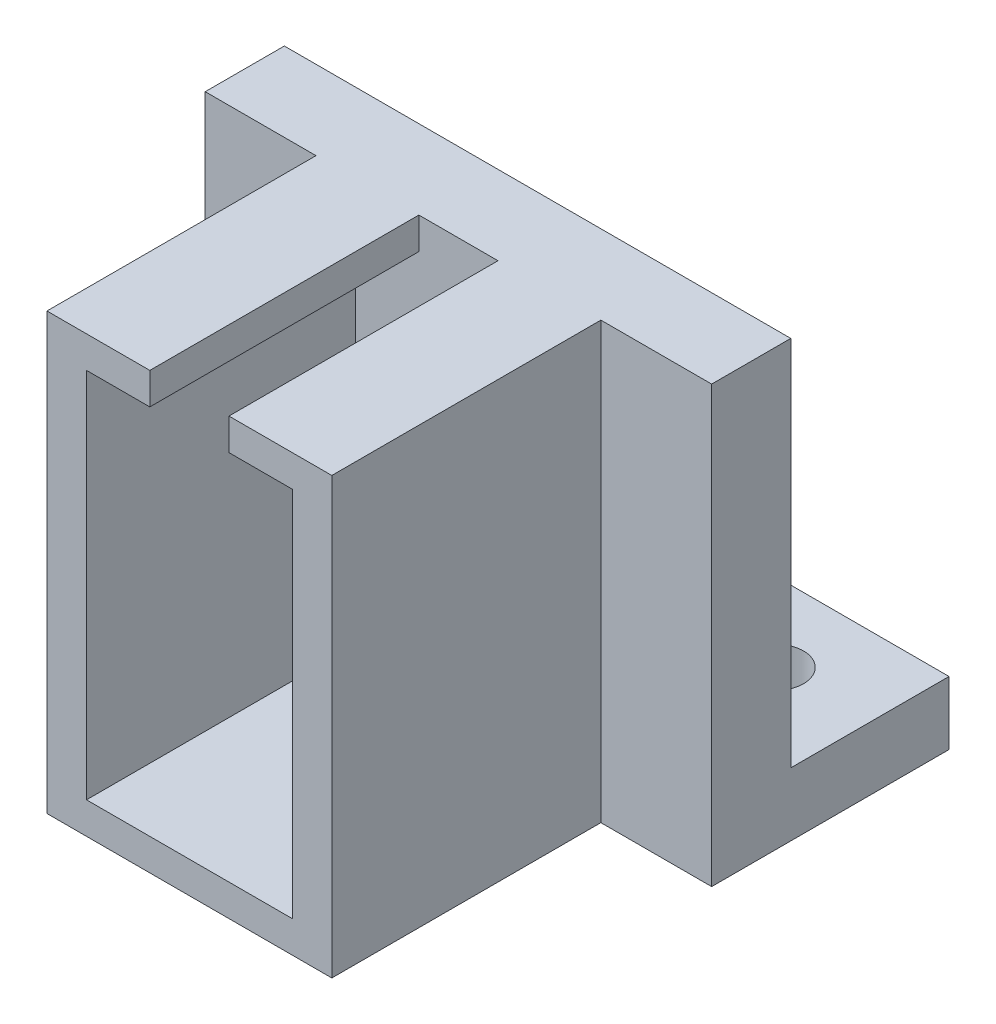
SolidWorks part; units mm, degrees
note: The reader was unsure of these and kept them because the rebuilt part matched: shared geometry of "Sketch1<3>".
ref_plane "Front Plane" through (0, 0, 0) normal (0, 0, 1) x (1, 0, 0)
ref_plane "Top Plane" through (0, 0, 0) normal (0, 1, 0) x (1, 0, 0)
ref_plane "Right Plane" through (0, 0, 0) normal (1, 0, 0) x (0, 0, -1)
sketch "Sketch1" plane through (0, 0, 0) normal (0, 1, 0) x (1, 0, 0)
  line L0 (-16, 0) -> (16, 0)
  line L1 (16, 0) -> (16, 10)
  line L2 (16, 10) -> (-16, 10)
  line L3 (-16, 10) -> (-16, 0)
  line L4 (-16, 0) -> (-16, -5)
  line L5 (-16, -5) -> (16, -5)
  line L6 (16, -5) -> (16, 0)
  line L7 (-10, 5) -> (10, 5) construction
  point P7 (-10, 5)
  point P8 (10, 5)
  point P11 (0, 0)
  point P12 (0, 5)
  dimension "D1" = 20
  dimension "D2" = 10
  dimension "D3" = 32
  dimension "D4" = 5
extrude "Boss-Extrude1" add sketch "Sketch1" along normal blind 4
extrude "Boss-Extrude2" add sketch "Sketch1<3>" along normal blind 23.5 from surface at 4 contours L5 L6 L0 L4 starting at face at (0, 4, -2.5)
sketch "Sketch1<3>" plane through (0, 0, 0) normal (0, 1, 0) x (1, 0, 0) same geometry as "Sketch1"
sketch "Sketch2" plane through (0, 0, 5) normal (0, 0, 1) x (1, 0, 0)
  line L0 (-16, 0) -> (16, 0) construction
  line L1 (-6.5, 25.5) -> (6.5, 25.5)
  line L2 (-6.5, 25.5) -> (-6.5, 2)
  line L3 (-6.5, 2) -> (6.5, 2)
  line L4 (6.5, 25.5) -> (6.5, 2)
  line L5 (-6.5, 25.5) -> (6.5, 2) construction
  line L6 (-6.5, 2) -> (6.5, 25.5) construction
  line L7 (-9, 0) -> (9, 0)
  line L8 (-9, 0) -> (-9, 27.5)
  line L9 (-9, 27.5) -> (9, 27.5)
  line L10 (9, 0) -> (9, 27.5)
  line L11 (-9, 0) -> (9, 27.5) construction
  line L12 (-9, 27.5) -> (9, 0) construction
  line L13 (16, 27.5) -> (-16, 27.5) construction
  line L14 (-2.5, 27.5) -> (-2.5, 25.5)
  line L15 (2.5, 25.5) -> (2.5, 27.5)
  line L16 (0, 25.5) -> (0, 27.5) construction
  point P0 (0, 13.75)
  point P7 (0, 13.75)
  dimension "D1" = 13
  dimension "D2" = 23.5
  dimension "D3" = 2.5
  dimension "D4" = 5
extrude "Boss-Extrude3" add sketch "Sketch2" along normal blind 17
hole_wizard "M3 Clearance Hole1" positions "Sketch3" profile "Sketch4" hole size "M3" standard "ISO"
sketch "Sketch3" plane through (0, 4, 0) normal (0, 1, 0) x (1, 0, 0)
  point P0 (-10, 5)
  point P3 (10, 5)
sketch "Sketch4" plane through (-10, 4, -5) normal (1, 0, 0) x (0, 0, 1)
  line L0 (0, 0) -> (0, 11.0815)
  line L1 (0, 11.0815) -> (1.8, 10)
  line L2 (1.8, 10) -> (1.8, 0)
  line L5 (1.8, 0) -> (0, 0)
  line L10 (0, 11.0815) -> (-1.8, 10) construction
  line L11 (0, -6.35) -> (0, 107.95) construction
  dimension "Hole Dia." = 3.6
  dimension "Hole Depth" = 10
  dimension "Drill Angle" = 118
